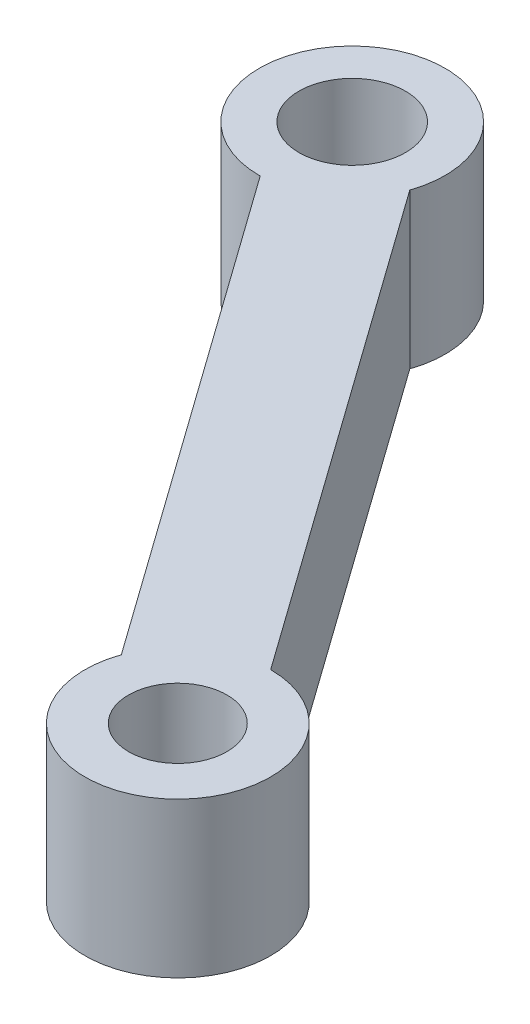
SolidWorks part; units mm, degrees
ref_plane "Front Plane" through (0, 0, 0) normal (0, 0, 1) x (1, 0, 0)
ref_plane "Top Plane" through (0, 0, 0) normal (0, 1, 0) x (1, 0, 0)
ref_plane "Right Plane" through (0, 0, 0) normal (1, 0, 0) x (0, 0, -1)
sketch "Croquis2" plane through (0, 0, 0) normal (0, 1, 0) x (1, 0, 0)
  line L0 (45, 0) -> (46.0553, 0) construction
  line L1 (-75, -40) -> (55, -40)
  line L2 (-75, -40) -> (-75, 40)
  line L3 (-75, 40) -> (55, 40)
  line L4 (75, -20) -> (75, 20)
  line L5 (45, 0) -> (46.0553, 0) construction
  line L6 (67, 26.7583) -> (67, -26.7583)
  line L7 (45, -30) -> (-50, -30)
  line L8 (45, -30) -> (45, 30)
  line L9 (45, 30) -> (-50, 30)
  line L10 (-50, -30) -> (-50, 30)
  line L11 (67, -26.7583) -> (67, 26.7583)
  line L13 (67, 26.7583) -> (61, 26.7583)
  line L15 (46.228, -1.6) -> (46.2586, -1.7343)
  line L16 (61.1553, 0) -> (61.0553, 0) construction
  line L17 (54.1602, 2.3742) -> (54.0439, 2.2986)
  line L18 (54.0439, 2.2986) -> (53.9684, 2.4149)
  line L19 (53.9087, 2.4244) -> (53.801, 2.3371)
  line L20 (53.801, 2.3371) -> (53.7137, 2.4449)
  line L21 (53.6534, 2.448) -> (53.5553, 2.35)
  line L22 (53.5553, 2.35) -> (53.4573, 2.448)
  line L23 (53.3969, 2.4449) -> (53.3097, 2.3371)
  line L24 (53.3097, 2.3371) -> (53.2019, 2.4244)
  line L25 (53.1422, 2.4149) -> (53.0667, 2.2986)
  line L26 (53.0667, 2.2986) -> (52.9505, 2.3742)
  line L27 (52.8921, 2.3585) -> (52.8291, 2.235)
  line L28 (52.8291, 2.235) -> (52.7056, 2.2979)
  line L29 (52.6492, 2.2763) -> (52.5995, 2.1468)
  line L30 (52.5995, 2.1468) -> (52.4701, 2.1965)
  line L31 (52.4162, 2.1691) -> (52.3803, 2.0352)
  line L32 (52.3803, 2.0352) -> (52.2464, 2.071)
  line L33 (52.1957, 2.0381) -> (52.174, 1.9012)
  line L34 (52.174, 1.9012) -> (52.0371, 1.9229)
  line L35 (51.9901, 1.8848) -> (51.9829, 1.7464)
  line L36 (51.9829, 1.7464) -> (51.8444, 1.7536)
  line L37 (51.8017, 1.7109) -> (51.8089, 1.5725)
  line L38 (51.8089, 1.5725) -> (51.6705, 1.5652)
  line L39 (51.6325, 1.5182) -> (51.6541, 1.3813)
  line L40 (51.6541, 1.3813) -> (51.5172, 1.3596)
  line L41 (51.4843, 1.3089) -> (51.5202, 1.175)
  line L42 (51.5202, 1.175) -> (51.3862, 1.1391)
  line L43 (51.3588, 1.0853) -> (51.4085, 0.9558)
  line L44 (51.4085, 0.9558) -> (51.2791, 0.9061)
  line L45 (51.2574, 0.8497) -> (51.3203, 0.7262)
  line L46 (51.3203, 0.7262) -> (51.1968, 0.6632)
  line L47 (51.1812, 0.6049) -> (51.2567, 0.4886)
  line L48 (51.2567, 0.4886) -> (51.1404, 0.4131)
  line L49 (51.1309, 0.3534) -> (51.2182, 0.2456)
  line L50 (51.2182, 0.2456) -> (51.1105, 0.1584)
  line L51 (51.1073, 0.098) -> (51.2053, 0)
  line L52 (51.2053, 0) -> (51.1073, -0.098)
  line L53 (51.1105, -0.1584) -> (51.2182, -0.2456)
  line L54 (51.2182, -0.2456) -> (51.1309, -0.3534)
  line L55 (51.1404, -0.4131) -> (51.2567, -0.4886)
  line L56 (51.2567, -0.4886) -> (51.1812, -0.6049)
  line L57 (51.1968, -0.6632) -> (51.3203, -0.7262)
  line L58 (51.3203, -0.7262) -> (51.2574, -0.8497)
  line L59 (51.2791, -0.9061) -> (51.4085, -0.9558)
  line L60 (51.4085, -0.9558) -> (51.3588, -1.0853)
  line L61 (51.3862, -1.1391) -> (51.5202, -1.175)
  line L62 (51.5202, -1.175) -> (51.4843, -1.3089)
  line L63 (51.5172, -1.3596) -> (51.6541, -1.3813)
  line L64 (51.6541, -1.3813) -> (51.6325, -1.5182)
  line L65 (51.6705, -1.5652) -> (51.8089, -1.5725)
  line L66 (51.8089, -1.5725) -> (51.8017, -1.7109)
  line L67 (51.8444, -1.7536) -> (51.9829, -1.7464)
  line L68 (51.9829, -1.7464) -> (51.9901, -1.8848)
  line L69 (52.0371, -1.9229) -> (52.174, -1.9012)
  line L70 (52.174, -1.9012) -> (52.1957, -2.0381)
  line L71 (52.2464, -2.071) -> (52.3803, -2.0352)
  line L72 (52.3803, -2.0352) -> (52.4162, -2.1691)
  line L73 (52.4701, -2.1965) -> (52.5995, -2.1468)
  line L74 (52.5995, -2.1468) -> (52.6492, -2.2763)
  line L75 (52.7056, -2.2979) -> (52.8291, -2.235)
  line L76 (52.8291, -2.235) -> (52.8921, -2.3585)
  line L77 (52.9505, -2.3742) -> (53.0667, -2.2986)
  line L78 (53.0667, -2.2986) -> (53.1422, -2.4149)
  line L79 (53.2019, -2.4244) -> (53.3097, -2.3371)
  line L80 (53.3097, -2.3371) -> (53.3969, -2.4449)
  line L81 (53.4573, -2.448) -> (53.5553, -2.35)
  line L82 (53.5553, -2.35) -> (53.6534, -2.448)
  line L83 (53.7137, -2.4449) -> (53.801, -2.3371)
  line L84 (53.801, -2.3371) -> (53.9087, -2.4244)
  line L85 (53.9684, -2.4149) -> (54.0439, -2.2986)
  line L86 (54.0439, -2.2986) -> (54.1602, -2.3742)
  line L87 (54.2186, -2.3585) -> (54.2815, -2.235)
  line L88 (54.2815, -2.235) -> (54.4051, -2.2979)
  line L89 (54.4615, -2.2763) -> (54.5112, -2.1468)
  line L90 (54.5112, -2.1468) -> (54.6406, -2.1965)
  line L91 (54.6944, -2.1691) -> (54.7303, -2.0352)
  line L92 (54.7303, -2.0352) -> (54.8643, -2.071)
  line L93 (54.9149, -2.0381) -> (54.9366, -1.9012)
  line L94 (54.9366, -1.9012) -> (55.0736, -1.9229)
  line L95 (55.1205, -1.8848) -> (55.1278, -1.7464)
  line L96 (55.1278, -1.7464) -> (55.2662, -1.7536)
  line L97 (55.309, -1.7109) -> (55.3017, -1.5725)
  line L98 (55.3017, -1.5725) -> (55.4402, -1.5652)
  line L99 (55.4782, -1.5182) -> (55.4565, -1.3813)
  line L100 (55.4565, -1.3813) -> (55.5935, -1.3596)
  line L101 (55.6264, -1.3089) -> (55.5905, -1.175)
  line L102 (55.5905, -1.175) -> (55.7244, -1.1391)
  line L103 (55.7518, -1.0853) -> (55.7022, -0.9558)
  line L104 (55.7022, -0.9558) -> (55.8316, -0.9061)
  line L105 (55.8533, -0.8497) -> (55.7903, -0.7262)
  line L106 (55.7903, -0.7262) -> (55.9138, -0.6632)
  line L107 (55.9295, -0.6049) -> (55.854, -0.4886)
  line L108 (55.854, -0.4886) -> (55.9703, -0.4131)
  line L109 (55.9797, -0.3534) -> (55.8925, -0.2456)
  line L110 (55.8925, -0.2456) -> (56.0002, -0.1584)
  line L111 (56.0034, -0.098) -> (55.9053, 0)
  line L112 (55.9053, 0) -> (56.0034, 0.098)
  line L113 (56.0002, 0.1584) -> (55.8925, 0.2456)
  line L114 (55.8925, 0.2456) -> (55.9797, 0.3534)
  line L115 (55.9703, 0.4131) -> (55.854, 0.4886)
  line L116 (55.854, 0.4886) -> (55.9295, 0.6049)
  line L117 (55.9138, 0.6632) -> (55.7903, 0.7262)
  line L118 (55.7903, 0.7262) -> (55.8533, 0.8497)
  line L119 (55.8316, 0.9061) -> (55.7022, 0.9558)
  line L120 (55.7022, 0.9558) -> (55.7518, 1.0853)
  line L121 (55.7244, 1.1391) -> (55.5905, 1.175)
  line L122 (55.5905, 1.175) -> (55.6264, 1.3089)
  line L123 (55.5935, 1.3596) -> (55.4565, 1.3813)
  line L124 (55.4565, 1.3813) -> (55.4782, 1.5182)
  line L125 (55.4402, 1.5652) -> (55.3017, 1.5725)
  line L126 (55.3017, 1.5725) -> (55.309, 1.7109)
  line L127 (55.2662, 1.7536) -> (55.1278, 1.7464)
  line L128 (55.1278, 1.7464) -> (55.1205, 1.8848)
  line L129 (55.0736, 1.9229) -> (54.9366, 1.9012)
  line L130 (54.9366, 1.9012) -> (54.9149, 2.0381)
  line L131 (54.8643, 2.071) -> (54.7303, 2.0352)
  line L132 (54.7303, 2.0352) -> (54.6944, 2.1691)
  line L133 (54.6406, 2.1965) -> (54.5112, 2.1468)
  line L134 (54.5112, 2.1468) -> (54.4615, 2.2763)
  line L135 (54.4051, 2.2979) -> (54.2815, 2.235)
  line L136 (54.2815, 2.235) -> (54.2186, 2.3585)
  line L137 (53.5553, 0) -> (53.5553, -7.5) construction
  line L139 (65.0006, 25.8237) -> (59.5501, 25.8237) construction
  line L141 (61.0553, 0) -> (67, 0) construction
  line L142 (59.0553, 0) -> (53.5553, 0) construction
  line L143 (48.0553, 0) -> (53.5553, 0) construction
  line L144 (48.0553, 0) -> (59.0553, 0) construction
  line L145 (60.701, 2.278) -> (60.8827, 1.6)
  line L146 (61, 24.889) -> (61, 23.889)
  line L149 (61, 22.0197) -> (61, 21.0197)
  line L152 (61, 19.1504) -> (61, 18.1504)
  line L154 (59.5501, 17.5667) -> (59.5501, 16.8648)
  line L155 (61, 16.2811) -> (61, 15.2811)
  line L157 (59.5501, 14.6974) -> (59.5501, 13.9955)
  line L158 (61, 13.4118) -> (61, 12.4118)
  line L160 (59.5501, 11.8282) -> (59.5501, 11.1262)
  line L161 (61, 10.5425) -> (61, 9.5425)
  line L163 (59.5501, 8.9589) -> (59.5501, 8.2569)
  line L164 (61, 7.6732) -> (61, 6.6732)
  line L166 (59.5501, 6.0896) -> (59.5501, 5.3876)
  line L167 (61, 4.8039) -> (61, 3.8039)
  line L169 (59.5501, 3.2203) -> (59.5501, 2.5183)
  line L170 (61, 1.9346) -> (61, 0.9346)
  line L172 (59.5501, 0.351) -> (59.5501, -0.351)
  line L173 (61, -0.9346) -> (61, -1.9346)
  line L175 (59.5501, -2.5183) -> (59.5501, -3.2203)
  line L176 (61, -3.8039) -> (61, -4.8039)
  line L178 (59.5501, -5.3876) -> (59.5501, -6.0896)
  line L179 (61, -6.6732) -> (61, -7.6732)
  line L181 (59.5501, -8.2569) -> (59.5501, -8.9589)
  line L182 (61, -9.5425) -> (61, -10.5425)
  line L184 (59.5501, -11.1262) -> (59.5501, -11.8282)
  line L185 (61, -12.4118) -> (61, -13.4118)
  line L187 (59.5501, -13.9955) -> (59.5501, -14.6974)
  line L188 (61, -15.2811) -> (61, -16.2811)
  line L190 (59.5501, -16.8648) -> (59.5501, -17.5667)
  line L191 (61, -18.1504) -> (61, -19.1504)
  line L194 (61, -21.0197) -> (61, -22.0197)
  line L197 (61, -23.889) -> (61, -24.889)
  line L200 (64, 26.7583) -> (64, 26.3977) construction
  line L203 (61, -26.7583) -> (67, -26.7583)
  line L204 (75, 20) -> (67, 20) construction
  line L205 (61, -26.7583) -> (61, -27.7583) [skipped]
  line L206 (-50, 0) -> (-75, 0) construction
  line L207 (75, -20) -> (67, -20) construction
  line L208 (50, -40) -> (50, 40) construction
  line L209 (50, -35) -> (50, -43.5216) construction
  line L210 (53.5731, -35) -> (53.5731, -43.5216)
  line L211 (46.4269, -35) -> (46.4269, -43.5216)
  line L212 (50.0036, 34.1275) -> (50.0036, 40.0656) construction
  line L213 (53.6852, 34.1275) -> (53.5731, 43.5216)
  line L214 (46.4269, 35) -> (46.4269, 43.5216)
  line L215 (-50, -30) -> (-47.1716, -27.1716) construction
  line L221 (-50, -30) -> (-47.1716, -30)
  line L222 (-50, -30) -> (-50, -27.1716)
  line L223 (46.4269, -43.5216) -> (46.4269, -48.5216)
  line L224 (53.5731, -43.5216) -> (53.5731, -48.5216)
  line L225 (46.4269, -48.5216) -> (53.5731, -48.5216)
  line L226 (53.5731, 43.5216) -> (53.5731, 48.5216)
  line L227 (46.4269, 43.5216) -> (46.4269, 48.5216)
  line L228 (46.4269, 48.5216) -> (53.5731, 48.5216)
  line L229 (50, 43.0304) -> (64, 23.3977) construction
  line L232 (46.4269, 48.5216) -> (53.5731, 48.5216)
  line L233 (46.4269, 48.5216) -> (46.4269, 46.5216)
  line L234 (53.5731, 48.5216) -> (53.5731, 46.5216)
  line L235 (46.4269, 46.5216) -> (53.5731, 46.5216)
  line L236 (46.4269, -46.5216) -> (53.5731, -46.5216)
  line L239 (61, 19.1504) -> (67, 19.1504)
  line L240 (61, 26.7583) -> (61, 19.1504)
  line L241 (50.0036, 40.0656) -> (61.1732, 24.4022)
  line L242 (52.8363, 42.0529) -> (64, 26.3977)
  line L243 (48.6009, 42.0327) -> (62.6009, 22.4) construction
  line L244 (51.4182, 44.0416) -> (65.4182, 24.409) construction
  line L245 (61, 24.889) -> (61, 26.7583)
  line L246 (64, 25.8237) -> (64, -26.7583) construction
  line L248 (-70.5, -35) -> (-54.5, -35)
  line L249 (61, -26.7583) -> (61, -19.1504)
  line L250 (61, -19.1504) -> (67, -19.1504)
  line L251 (-50, -27.1716) -> (-47.1716, -27.1716)
  line L252 (-47.1716, -30) -> (-47.1716, -27.1716)
  line L253 (-2.5, -30) -> (-2.5, 30) construction
  line L254 (-70.5, -35) -> (-70.5, -40)
  line L255 (-54.5, 35) -> (-70.5, 35)
  line L260 (-54.5, 35) -> (-54.5, -35)
  line L261 (-54.5, -35) -> (-70.5, -35)
  line L262 (-70.5, 35) -> (-70.5, -35)
  line L263 (-54.5, 35) -> (-70.5, -35) construction
  line L264 (-54.5, -35) -> (-70.5, 35) construction
  line L265 (-70.5, -40) -> (-54.5, -40)
  line L266 (-54.5, -35) -> (-54.5, -40)
  line L267 (-70.5, 35) -> (-54.5, 35)
  line L268 (-70.5, 35) -> (-70.5, 40)
  line L269 (-70.5, 40) -> (-54.5, 40)
  line L270 (-54.5, 35) -> (-54.5, 40)
  circle A0 centre (53.5553, 0) radius 7.5
  arc A1 (53.9684, 2.4149) -> (53.9087, 2.4244) centre (53.5553, 0) ccw
  arc A2 (53.7137, 2.4449) -> (53.6534, 2.448) centre (53.5553, 0) ccw
  arc A3 (53.4573, 2.448) -> (53.3969, 2.4449) centre (53.5553, 0) ccw
  arc A4 (53.2019, 2.4244) -> (53.1422, 2.4149) centre (53.5553, 0) ccw
  arc A5 (52.9505, 2.3742) -> (52.8921, 2.3585) centre (53.5553, 0) ccw
  arc A6 (52.7056, 2.2979) -> (52.6492, 2.2763) centre (53.5553, 0) ccw
  arc A7 (52.4701, 2.1965) -> (52.4162, 2.1691) centre (53.5553, 0) ccw
  arc A8 (52.2464, 2.071) -> (52.1957, 2.0381) centre (53.5553, 0) ccw
  arc A9 (52.0371, 1.9229) -> (51.9901, 1.8848) centre (53.5553, 0) ccw
  arc A10 (51.8444, 1.7536) -> (51.8017, 1.7109) centre (53.5553, 0) ccw
  arc A11 (51.6705, 1.5652) -> (51.6325, 1.5182) centre (53.5553, 0) ccw
  arc A12 (51.5172, 1.3596) -> (51.4843, 1.3089) centre (53.5553, 0) ccw
  arc A13 (51.3862, 1.1391) -> (51.3588, 1.0853) centre (53.5553, 0) ccw
  arc A14 (51.2791, 0.9061) -> (51.2574, 0.8497) centre (53.5553, 0) ccw
  arc A15 (51.1968, 0.6632) -> (51.1812, 0.6049) centre (53.5553, 0) ccw
  arc A16 (51.1404, 0.4131) -> (51.1309, 0.3534) centre (53.5553, 0) ccw
  arc A17 (51.1105, 0.1584) -> (51.1073, 0.098) centre (53.5553, 0) ccw
  arc A18 (51.1073, -0.098) -> (51.1105, -0.1584) centre (53.5553, 0) ccw
  arc A19 (51.1309, -0.3534) -> (51.1404, -0.4131) centre (53.5553, 0) ccw
  arc A20 (51.1812, -0.6049) -> (51.1968, -0.6632) centre (53.5553, 0) ccw
  arc A21 (51.2574, -0.8497) -> (51.2791, -0.9061) centre (53.5553, 0) ccw
  arc A22 (51.3588, -1.0853) -> (51.3862, -1.1391) centre (53.5553, 0) ccw
  arc A23 (51.4843, -1.3089) -> (51.5172, -1.3596) centre (53.5553, 0) ccw
  arc A24 (51.6325, -1.5182) -> (51.6705, -1.5652) centre (53.5553, 0) ccw
  arc A25 (51.8017, -1.7109) -> (51.8444, -1.7536) centre (53.5553, 0) ccw
  arc A26 (51.9901, -1.8848) -> (52.0371, -1.9229) centre (53.5553, 0) ccw
  arc A27 (52.1957, -2.0381) -> (52.2464, -2.071) centre (53.5553, 0) ccw
  arc A28 (52.4162, -2.1691) -> (52.4701, -2.1965) centre (53.5553, 0) ccw
  arc A29 (52.6492, -2.2763) -> (52.7056, -2.2979) centre (53.5553, 0) ccw
  arc A30 (52.8921, -2.3585) -> (52.9505, -2.3742) centre (53.5553, 0) ccw
  arc A31 (53.1422, -2.4149) -> (53.2019, -2.4244) centre (53.5553, 0) ccw
  arc A32 (53.3969, -2.4449) -> (53.4573, -2.448) centre (53.5553, 0) ccw
  arc A33 (53.6534, -2.448) -> (53.7137, -2.4449) centre (53.5553, 0) ccw
  arc A34 (53.9087, -2.4244) -> (53.9684, -2.4149) centre (53.5553, 0) ccw
  arc A35 (54.1602, -2.3742) -> (54.2186, -2.3585) centre (53.5553, 0) ccw
  arc A36 (54.4051, -2.2979) -> (54.4615, -2.2763) centre (53.5553, 0) ccw
  arc A37 (54.6406, -2.1965) -> (54.6944, -2.1691) centre (53.5553, 0) ccw
  arc A38 (54.8643, -2.071) -> (54.9149, -2.0381) centre (53.5553, 0) ccw
  arc A39 (55.0736, -1.9229) -> (55.1205, -1.8848) centre (53.5553, 0) ccw
  arc A40 (55.2662, -1.7536) -> (55.309, -1.7109) centre (53.5553, 0) ccw
  arc A41 (55.4402, -1.5652) -> (55.4782, -1.5182) centre (53.5553, 0) ccw
  arc A42 (55.5935, -1.3596) -> (55.6264, -1.3089) centre (53.5553, 0) ccw
  arc A43 (55.7244, -1.1391) -> (55.7518, -1.0853) centre (53.5553, 0) ccw
  arc A44 (55.8316, -0.9061) -> (55.8533, -0.8497) centre (53.5553, 0) ccw
  arc A45 (55.9138, -0.6632) -> (55.9295, -0.6049) centre (53.5553, 0) ccw
  arc A46 (55.9703, -0.4131) -> (55.9797, -0.3534) centre (53.5553, 0) ccw
  arc A47 (56.0002, -0.1584) -> (56.0034, -0.098) centre (53.5553, 0) ccw
  arc A48 (56.0034, 0.098) -> (56.0002, 0.1584) centre (53.5553, 0) ccw
  arc A49 (55.9797, 0.3534) -> (55.9703, 0.4131) centre (53.5553, 0) ccw
  arc A50 (55.9295, 0.6049) -> (55.9138, 0.6632) centre (53.5553, 0) ccw
  arc A51 (55.8533, 0.8497) -> (55.8316, 0.9061) centre (53.5553, 0) ccw
  arc A52 (55.7518, 1.0853) -> (55.7244, 1.1391) centre (53.5553, 0) ccw
  arc A53 (55.6264, 1.3089) -> (55.5935, 1.3596) centre (53.5553, 0) ccw
  arc A54 (55.4782, 1.5182) -> (55.4402, 1.5652) centre (53.5553, 0) ccw
  arc A55 (55.309, 1.7109) -> (55.2662, 1.7536) centre (53.5553, 0) ccw
  arc A56 (55.1205, 1.8848) -> (55.0736, 1.9229) centre (53.5553, 0) ccw
  arc A57 (54.9149, 2.0381) -> (54.8643, 2.071) centre (53.5553, 0) ccw
  arc A58 (54.6944, 2.1691) -> (54.6406, 2.1965) centre (53.5553, 0) ccw
  arc A59 (54.4615, 2.2763) -> (54.4051, 2.2979) centre (53.5553, 0) ccw
  arc A60 (54.2186, 2.3585) -> (54.1602, 2.3742) centre (53.5553, 0) ccw
  circle A61 centre (53.5553, 0) radius 2.25
  arc A62 (55, 40) -> (75, 20) centre (55, 20) cw
  arc A63 (55, -40) -> (75, -20) centre (55, -20) ccw
  circle A64 centre (53.5553, 0) radius 5.5
  arc A65 (54.0553, -5.4772) -> (55.1553, -7.3273) centre (59.6317, -3.4139) ccw
  arc A66 (53.0553, -5.4772) -> (51.9553, -7.3273) centre (47.479, -3.4139) cw
  arc A67 (50.3837, -4.4934) -> (48.506, -5.5457) centre (46.5861, 0.0817) cw
  arc A68 (51.2497, -4.9934) -> (51.2773, -7.1457) centre (57.1107, -5.9946) ccw
  arc A69 (48.5619, -2.3056) -> (46.4097, -2.278) centre (47.5607, 3.5553) cw
  arc A70 (49.0619, -3.1716) -> (48.0097, -5.0493) centre (53.637, -6.9692) ccw
  arc A71 (48.0781, 0.5) -> (46.228, 1.6) centre (50.1415, 6.0763) cw
  arc A72 (48.0781, -0.5) -> (46.228, -1.6) centre (50.1415, -6.0763) ccw
  arc A73 (49.0619, 3.1716) -> (48.0097, 5.0493) centre (53.637, 6.9692) cw
  arc A74 (48.5619, 2.3056) -> (46.4097, 2.278) centre (47.5607, -3.5553) ccw
  arc A75 (51.2497, 4.9934) -> (51.2773, 7.1457) centre (57.1107, 5.9946) cw
  arc A76 (50.3837, 4.4934) -> (48.506, 5.5457) centre (46.5861, -0.0817) ccw
  arc A77 (54.0553, 5.4772) -> (55.1553, 7.3273) centre (59.6317, 3.4139) cw
  arc A78 (53.0553, 5.4772) -> (51.9553, 7.3273) centre (47.479, 3.4139) ccw
  arc A79 (56.727, 4.4934) -> (58.6046, 5.5457) centre (60.5245, -0.0817) cw
  arc A80 (55.8609, 4.9934) -> (55.8334, 7.1457) centre (50, 5.9946) ccw
  arc A81 (58.5487, 2.3056) -> (60.701, 2.278) centre (59.55, -3.5553) cw
  arc A82 (58.0487, 3.1716) -> (59.101, 5.0493) centre (53.4736, 6.9692) ccw
  arc A83 (59.0326, -0.5) -> (60.8827, -1.6) centre (56.9692, -6.0763) cw
  arc A84 (59.0326, 0.5) -> (60.8827, 1.6) centre (56.9692, 6.0763) ccw
  arc A85 (58.0487, -3.1716) -> (59.101, -5.0493) centre (53.4736, -6.9692) cw
  arc A86 (58.5487, -2.3056) -> (60.701, -2.278) centre (59.55, 3.5553) ccw
  arc A89 (55.8609, -4.9934) -> (55.8334, -7.1457) centre (50, -5.9946) cw
  arc A90 (56.727, -4.4934) -> (58.6046, -5.5457) centre (60.5245, 0.0817) ccw
  arc A95 (61, 16.2811) -> (59.5501, 16.8648) centre (62.2327, 21.4358) cw
  arc A96 (61, 18.1504) -> (59.5501, 17.5667) centre (62.2327, 12.9958) ccw
  arc A97 (61, 13.4118) -> (59.5501, 13.9955) centre (62.2327, 18.5665) cw
  arc A98 (61, 15.2811) -> (59.5501, 14.6974) centre (62.2327, 10.1265) ccw
  arc A99 (61, 10.5425) -> (59.5501, 11.1262) centre (62.2327, 15.6972) cw
  arc A100 (61, 12.4118) -> (59.5501, 11.8282) centre (62.2327, 7.2572) ccw
  arc A101 (61, 7.6732) -> (59.5501, 8.2569) centre (62.2327, 12.8279) cw
  arc A102 (61, 9.5425) -> (59.5501, 8.9589) centre (62.2327, 4.3879) ccw
  arc A103 (61, 4.8039) -> (59.5501, 5.3876) centre (62.2327, 9.9586) cw
  arc A104 (61, 6.6732) -> (59.5501, 6.0896) centre (62.2327, 1.5186) ccw
  arc A105 (61, 1.9346) -> (59.5501, 2.5183) centre (62.2327, 7.0893) cw
  arc A106 (61, 3.8039) -> (59.5501, 3.2203) centre (62.2327, -1.3507) ccw
  arc A107 (61, -0.9346) -> (59.5501, -0.351) centre (62.2327, 4.22) cw
  arc A108 (61, 0.9346) -> (59.5501, 0.351) centre (62.2327, -4.22) ccw
  arc A109 (61, -3.8039) -> (59.5501, -3.2203) centre (62.2327, 1.3507) cw
  arc A110 (61, -1.9346) -> (59.5501, -2.5183) centre (62.2327, -7.0893) ccw
  arc A111 (61, -6.6732) -> (59.5501, -6.0896) centre (62.2327, -1.5186) cw
  arc A112 (61, -4.8039) -> (59.5501, -5.3876) centre (62.2327, -9.9586) ccw
  arc A113 (61, -9.5425) -> (59.5501, -8.9589) centre (62.2327, -4.3879) cw
  arc A114 (61, -7.6732) -> (59.5501, -8.2569) centre (62.2327, -12.8279) ccw
  arc A115 (61, -12.4118) -> (59.5501, -11.8282) centre (62.2327, -7.2572) cw
  arc A116 (61, -10.5425) -> (59.5501, -11.1262) centre (62.2327, -15.6972) ccw
  arc A117 (61, -15.2811) -> (59.5501, -14.6974) centre (62.2327, -10.1265) cw
  arc A118 (61, -13.4118) -> (59.5501, -13.9955) centre (62.2327, -18.5665) ccw
  arc A119 (61, -18.1504) -> (59.5501, -17.5667) centre (62.2327, -12.9958) cw
  arc A120 (61, -16.2811) -> (59.5501, -16.8648) centre (62.2327, -21.4358) ccw
  circle A128 centre (64, -23.889) radius 1.5875
  circle A129 centre (64, 23.3977) radius 1.5875
  circle A130 centre (69.4482, 20) radius 2.175
  circle A131 centre (69.4482, -20) radius 2.175
  circle A132 centre (50, -35) radius 1.5875
  circle A133 centre (50.0036, 34.1275) radius 1.5875
  arc A134 (53.5731, -35) -> (46.4269, -35) centre (50, -35) ccw
  arc A136 (53.6852, 34.1275) -> (46.4269, 35) centre (50.0036, 34.1275) cw
  circle A138 centre (50, 43.0304) radius 1.7203
  circle A139 centre (50, -43.5216) radius 1.7203
  arc A142 (52.4426, 44.7721) -> (47.5574, 41.2886) centre (50, 43.0304) ccw
  arc A143 (61.5574, 21.6559) -> (66.4426, 25.1395) centre (64, 23.3977) ccw
  arc A144 (52.8363, 42.0529) -> (50.0286, 40.0305) centre (50, 43.0304) ccw
  arc A145 (61.1732, 24.4022) -> (64, 26.3977) centre (64, 23.3977) ccw
  arc A146 (62.2582, 25.8403) -> (62.2351, 25.8237) centre (64, 23.3977) ccw
  circle A151 centre (-47.1716, -27.1716) radius 2
  circle A152 centre (42.1716, -27.1716) radius 2
  circle A153 centre (42.1716, 27.1716) radius 2
  circle A154 centre (-47.1716, 27.1716) radius 2
  point P5 (65.0006, 25.8237)
  point P6 (0, 0)
  point P13 (67, 0)
  point P20 (59.8563, -29.3308)
  point P216 (53.5553, -7.5)
  point P221 (53.5553, -5.5)
  point P283 (53.5553, 0)
  point P290 (59.5501, 25.8237)
  point P292 (61, 24.889)
  point P297 (53.5553, 0)
  point P409 (-62.5, 0)
  point P411 (-62.5, 0)
  point P415 (-62.5, 0)
  point P424 (50, -39.2608)
  point P434 (50, 39.2608)
  point P453 (57, 33.214)
  dimension "D6" = 15
  dimension "D9" = 6
  dimension "D10" = 11
  dimension "D13" = 30
  dimension "D20" = 1
  dimension "D22" = 3.175
  dimension "D23" = 3.175
  dimension "D8" = 4.35
  dimension "D25" = 3.175
  dimension "D30" = 5
  dimension "D32" = 3
  dimension "D18" = 4
  dimension "D2" = 80
  dimension "D3" = 30
  dimension "D4" = 60
  dimension "D5" = 12
  dimension "D7" = 8.5553
  dimension "D11" = 0.5
  dimension "D12" = 1.6
  dimension "D14" = 4
  dimension "D15" = 95
  dimension "2.25" = 22
  dimension "D16" = 1.8693
  dimension "D17" = 1.8693
  dimension "D19" = 0.702
  dimension "D24" = 16
  dimension "D26" = 5
  dimension "D27" = 5
  dimension "D28" = 130
  dimension "D31" = 2
  dimension "D21" = 19
extrude "Saliente-Extruir1" add sketch "Croquis2" against normal blind 5 contours L242 A144 A142 L241 L3 L213 A138 | L242 L213 L3 | L3 L241 L213 | L242 L3 L213 L241 L146 L240 L13 | A143 A145 L242 L13 L240 L146 L241 A129 region at (50.1124, 0, -40.0672) region at (52.4471, 0, -38.3053) region at (53.8396, 0, -40.3257) region at (57.8402, 0, -32.2255) region at (61.0874, 0, -24.767)
